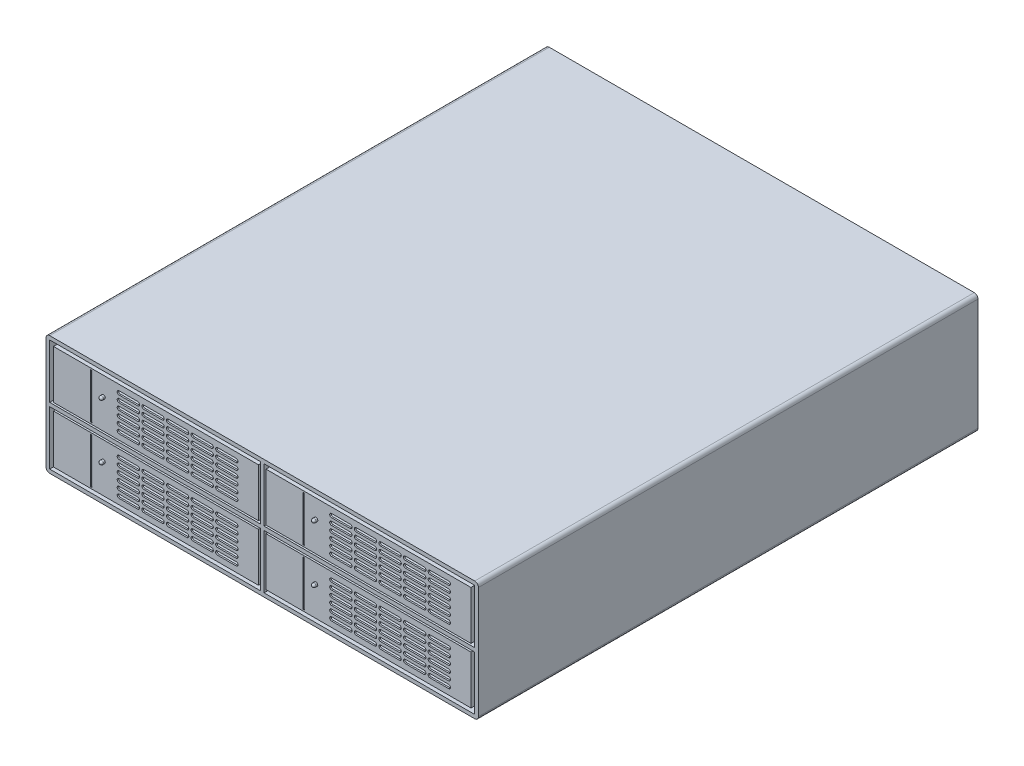
SolidWorks part; units mm, degrees
ref_plane "Front Plane" through (0, 0, 0) normal (0, 0, 1) x (1, 0, 0)
ref_plane "Top Plane" through (0, 0, 0) normal (0, 1, 0) x (1, 0, 0)
ref_plane "Right Plane" through (0, 0, 0) normal (1, 0, 0) x (0, 0, -1)
sketch "Sketch1" plane through (0, 0, 0) normal (0, 0, 1) x (1, 0, 0)
  line L1 (-73.66, 20.32) -> (73.66, 20.32)
  line L2 (-73.66, 20.32) -> (-73.66, -20.32)
  line L3 (-73.66, -20.32) -> (73.66, -20.32)
  line L4 (73.66, 20.32) -> (73.66, -20.32)
  line L5 (-73.66, 20.32) -> (73.66, -20.32) construction
  line L6 (-73.66, -20.32) -> (73.66, 20.32) construction
  point P0 (0, 0)
  dimension "D1" = 40.64
  dimension "D2" = 147.32
extrude "Boss-Extrude1" add sketch "Sketch1" against normal blind 170.18
sketch "Sketch2" plane through (0, 0, 0) normal (0, 0, 1) x (1, 0, 0)
  line L0 (73.66, 20.32) -> (-73.66, 20.32) construction
  line L1 (-71.12, 17.78) -> (-1.27, 17.78)
  line L2 (-71.12, 17.78) -> (-71.12, 1.27)
  line L3 (-71.12, 1.27) -> (-1.27, 1.27)
  line L4 (-1.27, 17.78) -> (-1.27, 1.27)
  line L5 (1.27, 17.78) -> (71.12, 17.78)
  line L6 (1.27, 17.78) -> (1.27, 1.27)
  line L7 (1.27, 1.27) -> (71.12, 1.27)
  line L8 (71.12, 17.78) -> (71.12, 1.27)
  line L9 (71.12, -1.27) -> (1.27, -1.27)
  line L10 (71.12, -1.27) -> (71.12, -17.78)
  line L11 (71.12, -17.78) -> (1.27, -17.78)
  line L12 (1.27, -1.27) -> (1.27, -17.78)
  line L13 (-1.27, -1.27) -> (-71.12, -1.27)
  line L14 (-1.27, -1.27) -> (-1.27, -17.78)
  line L15 (-1.27, -17.78) -> (-71.12, -17.78)
  line L16 (-71.12, -1.27) -> (-71.12, -17.78)
  line L17 (-73.66, 20.32) -> (-73.66, -20.32) construction
  line L18 (-73.66, -20.32) -> (73.66, -20.32) construction
  line L19 (73.66, -20.32) -> (73.66, 20.32) construction
  line L21 (-72.39, 19.05) -> (-0.635, 19.05)
  line L22 (-72.39, 19.05) -> (-72.39, 0.635)
  line L23 (-72.39, 0.635) -> (-0.635, 0.635)
  line L24 (-0.635, 19.05) -> (-0.635, 0.635)
  line L25 (-72.39, -0.635) -> (-0.635, -0.635)
  line L26 (-72.39, -0.635) -> (-72.39, -19.05)
  line L27 (-72.39, -19.05) -> (-0.635, -19.05)
  line L28 (-0.635, -0.635) -> (-0.635, -19.05)
  line L29 (0.635, -0.635) -> (72.39, -0.635)
  line L30 (0.635, -0.635) -> (0.635, -19.05)
  line L31 (0.635, -19.05) -> (72.39, -19.05)
  line L32 (72.39, -0.635) -> (72.39, -19.05)
  line L33 (72.39, 19.05) -> (0.635, 19.05)
  line L34 (72.39, 19.05) -> (72.39, 0.635)
  line L35 (72.39, 0.635) -> (0.635, 0.635)
  line L36 (0.635, 19.05) -> (0.635, 0.635)
  dimension "D1" = 2.54
  dimension "D2" = 2.54
  dimension "D3" = 2.54
  dimension "D4" = 2.54
  dimension "D5" = 2.54
  dimension "D6" = 2.54
  dimension "D7" = 2.54
  dimension "D8" = 2.54
  dimension "D9" = 2.54
  dimension "D10" = 16.51
  dimension "D11" = 2.54
  dimension "D12" = 16.51
  dimension "D13" = 2.54
  dimension "D14" = 2.54
  dimension "D15" = 69.85
  dimension "D16" = 69.85
  dimension "D17" = 1.27
  dimension "D18" = 1.27
  dimension "D19" = 1.27
  dimension "D20" = 1.27
  dimension "D21" = 0.635
  dimension "D22" = 0.635
  dimension "D23" = 1.27
  dimension "D24" = 1.27
  dimension "D25" = 0.635
  dimension "D26" = 0.635
  dimension "D27" = 1.27
  dimension "D28" = 0.635
  dimension "D29" = 1.27
  dimension "D30" = 0.635
  dimension "D31" = 0.635
  dimension "D32" = 1.27
extrude "Cut-Extrude1" cut sketch "Sketch2" against normal blind 152.4
fillet "Fillet1" radius 1.27 4 edges at (-73.66, 20.32, -85.09) (-73.66, -20.32, -85.09) (73.66, -20.32, -85.09) (73.66, 20.32, -85.09)
sketch "Sketch4" plane through (0, 0, 0) normal (0, 0, 1) x (1, 0, 0)
  line L0 (-73.66, 0) -> (73.66, 0) construction
  line L1 (-73.66, 19.05) -> (-73.66, -19.05) construction
  line L2 (73.66, -19.05) -> (73.66, 19.05) construction
  line L3 (-8.89, 3.81) -> (-15.24, 3.81) construction
  line L4 (-8.89, 3.175) -> (-15.24, 3.175)
  line L5 (-8.89, 4.445) -> (-15.24, 4.445)
  line L7 (-8.89, 6.096) -> (-15.24, 6.096) construction
  line L8 (-8.89, 5.461) -> (-15.24, 5.461)
  line L9 (-8.89, 6.731) -> (-15.24, 6.731)
  line L10 (-8.89, 8.382) -> (-15.24, 8.382) construction
  line L11 (-8.89, 7.747) -> (-15.24, 7.747)
  line L12 (-8.89, 9.017) -> (-15.24, 9.017)
  line L13 (-8.89, 10.668) -> (-15.24, 10.668) construction
  line L14 (-8.89, 10.033) -> (-15.24, 10.033)
  line L15 (-8.89, 11.303) -> (-15.24, 11.303)
  line L16 (-8.89, 12.954) -> (-15.24, 12.954) construction
  line L17 (-8.89, 12.319) -> (-15.24, 12.319)
  line L18 (-8.89, 13.589) -> (-15.24, 13.589)
  line L19 (-8.89, 15.24) -> (-15.24, 15.24) construction
  line L20 (-8.89, 14.605) -> (-15.24, 14.605)
  line L21 (-8.89, 15.875) -> (-15.24, 15.875)
  line L22 (-71.12, 1.27) -> (-1.27, 1.27) construction
  line L23 (-1.27, 1.27) -> (-1.27, 17.78) construction
  line L24 (-17.272, 3.81) -> (-23.622, 3.81) construction
  line L25 (-17.272, 3.175) -> (-23.622, 3.175)
  line L26 (-17.272, 4.445) -> (-23.622, 4.445)
  line L27 (-17.272, 6.096) -> (-23.622, 6.096) construction
  line L28 (-17.272, 5.461) -> (-23.622, 5.461)
  line L29 (-17.272, 6.731) -> (-23.622, 6.731)
  line L30 (-17.272, 8.382) -> (-23.622, 8.382) construction
  line L31 (-17.272, 7.747) -> (-23.622, 7.747)
  line L32 (-17.272, 9.017) -> (-23.622, 9.017)
  line L33 (-17.272, 10.668) -> (-23.622, 10.668) construction
  line L34 (-17.272, 10.033) -> (-23.622, 10.033)
  line L35 (-17.272, 11.303) -> (-23.622, 11.303)
  line L36 (-17.272, 12.954) -> (-23.622, 12.954) construction
  line L37 (-17.272, 12.319) -> (-23.622, 12.319)
  line L38 (-17.272, 13.589) -> (-23.622, 13.589)
  line L39 (-17.272, 15.24) -> (-23.622, 15.24) construction
  line L40 (-17.272, 14.605) -> (-23.622, 14.605)
  line L41 (-17.272, 15.875) -> (-23.622, 15.875)
  line L42 (-25.654, 3.81) -> (-32.004, 3.81) construction
  line L43 (-25.654, 3.175) -> (-32.004, 3.175)
  line L44 (-25.654, 4.445) -> (-32.004, 4.445)
  line L45 (-25.654, 6.096) -> (-32.004, 6.096) construction
  line L46 (-25.654, 5.461) -> (-32.004, 5.461)
  line L47 (-25.654, 6.731) -> (-32.004, 6.731)
  line L48 (-25.654, 8.382) -> (-32.004, 8.382) construction
  line L49 (-25.654, 7.747) -> (-32.004, 7.747)
  line L50 (-25.654, 9.017) -> (-32.004, 9.017)
  line L51 (-25.654, 10.668) -> (-32.004, 10.668) construction
  line L52 (-25.654, 10.033) -> (-32.004, 10.033)
  line L53 (-25.654, 11.303) -> (-32.004, 11.303)
  line L54 (-25.654, 12.954) -> (-32.004, 12.954) construction
  line L55 (-25.654, 12.319) -> (-32.004, 12.319)
  line L56 (-25.654, 13.589) -> (-32.004, 13.589)
  line L57 (-25.654, 15.24) -> (-32.004, 15.24) construction
  line L58 (-25.654, 14.605) -> (-32.004, 14.605)
  line L59 (-25.654, 15.875) -> (-32.004, 15.875)
  line L60 (-34.036, 3.81) -> (-40.386, 3.81) construction
  line L61 (-34.036, 3.175) -> (-40.386, 3.175)
  line L62 (-34.036, 4.445) -> (-40.386, 4.445)
  line L63 (-34.036, 6.096) -> (-40.386, 6.096) construction
  line L64 (-34.036, 5.461) -> (-40.386, 5.461)
  line L65 (-34.036, 6.731) -> (-40.386, 6.731)
  line L66 (-34.036, 8.382) -> (-40.386, 8.382) construction
  line L67 (-34.036, 7.747) -> (-40.386, 7.747)
  line L68 (-34.036, 9.017) -> (-40.386, 9.017)
  line L69 (-34.036, 10.668) -> (-40.386, 10.668) construction
  line L70 (-34.036, 10.033) -> (-40.386, 10.033)
  line L71 (-34.036, 11.303) -> (-40.386, 11.303)
  line L72 (-34.036, 12.954) -> (-40.386, 12.954) construction
  line L73 (-34.036, 12.319) -> (-40.386, 12.319)
  line L74 (-34.036, 13.589) -> (-40.386, 13.589)
  line L75 (-34.036, 15.24) -> (-40.386, 15.24) construction
  line L76 (-34.036, 14.605) -> (-40.386, 14.605)
  line L77 (-34.036, 15.875) -> (-40.386, 15.875)
  line L78 (-42.418, 3.81) -> (-48.768, 3.81) construction
  line L79 (-42.418, 3.175) -> (-48.768, 3.175)
  line L80 (-42.418, 4.445) -> (-48.768, 4.445)
  line L81 (-42.418, 6.096) -> (-48.768, 6.096) construction
  line L82 (-42.418, 5.461) -> (-48.768, 5.461)
  line L83 (-42.418, 6.731) -> (-48.768, 6.731)
  line L84 (-42.418, 8.382) -> (-48.768, 8.382) construction
  line L85 (-42.418, 7.747) -> (-48.768, 7.747)
  line L86 (-42.418, 9.017) -> (-48.768, 9.017)
  line L87 (-42.418, 10.668) -> (-48.768, 10.668) construction
  line L88 (-42.418, 10.033) -> (-48.768, 10.033)
  line L89 (-42.418, 11.303) -> (-48.768, 11.303)
  line L90 (-42.418, 12.954) -> (-48.768, 12.954) construction
  line L91 (-42.418, 12.319) -> (-48.768, 12.319)
  line L92 (-42.418, 13.589) -> (-48.768, 13.589)
  line L93 (-42.418, 15.24) -> (-48.768, 15.24) construction
  line L94 (-42.418, 14.605) -> (-48.768, 14.605)
  line L95 (-42.418, 15.875) -> (-48.768, 15.875)
  line L96 (-42.418, -15.24) -> (-48.768, -15.24) construction
  line L97 (-42.418, -14.605) -> (-48.768, -14.605)
  line L98 (-42.418, -15.875) -> (-48.768, -15.875)
  line L99 (-42.418, -12.954) -> (-48.768, -12.954) construction
  line L100 (-42.418, -12.319) -> (-48.768, -12.319)
  line L101 (-42.418, -13.589) -> (-48.768, -13.589)
  line L102 (-42.418, -10.668) -> (-48.768, -10.668) construction
  line L103 (-42.418, -10.033) -> (-48.768, -10.033)
  line L104 (-42.418, -11.303) -> (-48.768, -11.303)
  line L105 (-42.418, -8.382) -> (-48.768, -8.382) construction
  line L106 (-42.418, -7.747) -> (-48.768, -7.747)
  line L107 (-42.418, -9.017) -> (-48.768, -9.017)
  line L108 (-42.418, -6.096) -> (-48.768, -6.096) construction
  line L109 (-42.418, -5.461) -> (-48.768, -5.461)
  line L110 (-42.418, -6.731) -> (-48.768, -6.731)
  line L111 (-42.418, -3.81) -> (-48.768, -3.81) construction
  line L112 (-42.418, -3.175) -> (-48.768, -3.175)
  line L113 (-42.418, -4.445) -> (-48.768, -4.445)
  line L114 (-34.036, -15.24) -> (-40.386, -15.24) construction
  line L115 (-34.036, -14.605) -> (-40.386, -14.605)
  line L116 (-34.036, -15.875) -> (-40.386, -15.875)
  line L117 (-34.036, -12.954) -> (-40.386, -12.954) construction
  line L118 (-34.036, -12.319) -> (-40.386, -12.319)
  line L119 (-34.036, -13.589) -> (-40.386, -13.589)
  line L120 (-34.036, -10.668) -> (-40.386, -10.668) construction
  line L121 (-34.036, -10.033) -> (-40.386, -10.033)
  line L122 (-34.036, -11.303) -> (-40.386, -11.303)
  line L123 (-34.036, -8.382) -> (-40.386, -8.382) construction
  line L124 (-34.036, -7.747) -> (-40.386, -7.747)
  line L125 (-34.036, -9.017) -> (-40.386, -9.017)
  line L126 (-34.036, -6.096) -> (-40.386, -6.096) construction
  line L127 (-34.036, -5.461) -> (-40.386, -5.461)
  line L128 (-34.036, -6.731) -> (-40.386, -6.731)
  line L129 (-34.036, -3.81) -> (-40.386, -3.81) construction
  line L130 (-34.036, -3.175) -> (-40.386, -3.175)
  line L131 (-34.036, -4.445) -> (-40.386, -4.445)
  line L132 (-25.654, -15.24) -> (-32.004, -15.24) construction
  line L133 (-25.654, -14.605) -> (-32.004, -14.605)
  line L134 (-25.654, -15.875) -> (-32.004, -15.875)
  line L135 (-25.654, -12.954) -> (-32.004, -12.954) construction
  line L136 (-25.654, -12.319) -> (-32.004, -12.319)
  line L137 (-25.654, -13.589) -> (-32.004, -13.589)
  line L138 (-25.654, -10.668) -> (-32.004, -10.668) construction
  line L139 (-25.654, -10.033) -> (-32.004, -10.033)
  line L140 (-25.654, -11.303) -> (-32.004, -11.303)
  line L141 (-25.654, -8.382) -> (-32.004, -8.382) construction
  line L142 (-25.654, -7.747) -> (-32.004, -7.747)
  line L143 (-25.654, -9.017) -> (-32.004, -9.017)
  line L144 (-25.654, -6.096) -> (-32.004, -6.096) construction
  line L145 (-25.654, -5.461) -> (-32.004, -5.461)
  line L146 (-25.654, -6.731) -> (-32.004, -6.731)
  line L147 (-25.654, -3.81) -> (-32.004, -3.81) construction
  line L148 (-25.654, -3.175) -> (-32.004, -3.175)
  line L149 (-25.654, -4.445) -> (-32.004, -4.445)
  line L150 (-17.272, -15.24) -> (-23.622, -15.24) construction
  line L151 (-17.272, -14.605) -> (-23.622, -14.605)
  line L152 (-17.272, -15.875) -> (-23.622, -15.875)
  line L153 (-17.272, -12.954) -> (-23.622, -12.954) construction
  line L154 (-17.272, -12.319) -> (-23.622, -12.319)
  line L155 (-17.272, -13.589) -> (-23.622, -13.589)
  line L156 (-17.272, -10.668) -> (-23.622, -10.668) construction
  line L157 (-17.272, -10.033) -> (-23.622, -10.033)
  line L158 (-17.272, -11.303) -> (-23.622, -11.303)
  line L159 (-17.272, -8.382) -> (-23.622, -8.382) construction
  line L160 (-17.272, -7.747) -> (-23.622, -7.747)
  line L161 (-17.272, -9.017) -> (-23.622, -9.017)
  line L162 (-17.272, -6.096) -> (-23.622, -6.096) construction
  line L163 (-17.272, -5.461) -> (-23.622, -5.461)
  line L164 (-17.272, -6.731) -> (-23.622, -6.731)
  line L165 (-17.272, -3.81) -> (-23.622, -3.81) construction
  line L166 (-17.272, -3.175) -> (-23.622, -3.175)
  line L167 (-17.272, -4.445) -> (-23.622, -4.445)
  line L168 (-8.89, -15.24) -> (-15.24, -15.24) construction
  line L169 (-8.89, -14.605) -> (-15.24, -14.605)
  line L170 (-8.89, -15.875) -> (-15.24, -15.875)
  line L171 (-8.89, -12.954) -> (-15.24, -12.954) construction
  line L172 (-8.89, -12.319) -> (-15.24, -12.319)
  line L173 (-8.89, -13.589) -> (-15.24, -13.589)
  line L174 (-8.89, -10.668) -> (-15.24, -10.668) construction
  line L175 (-8.89, -10.033) -> (-15.24, -10.033)
  line L176 (-8.89, -11.303) -> (-15.24, -11.303)
  line L177 (-8.89, -8.382) -> (-15.24, -8.382) construction
  line L178 (-8.89, -7.747) -> (-15.24, -7.747)
  line L179 (-8.89, -9.017) -> (-15.24, -9.017)
  line L180 (-8.89, -6.096) -> (-15.24, -6.096) construction
  line L181 (-8.89, -5.461) -> (-15.24, -5.461)
  line L182 (-8.89, -6.731) -> (-15.24, -6.731)
  line L183 (-8.89, -3.81) -> (-15.24, -3.81) construction
  line L184 (-8.89, -3.175) -> (-15.24, -3.175)
  line L185 (-8.89, -4.445) -> (-15.24, -4.445)
  line L186 (63.5, 3.81) -> (57.15, 3.81) construction
  line L187 (63.5, 3.175) -> (57.15, 3.175)
  line L188 (63.5, 4.445) -> (57.15, 4.445)
  line L189 (63.5, 6.096) -> (57.15, 6.096) construction
  line L190 (63.5, 5.461) -> (57.15, 5.461)
  line L191 (63.5, 6.731) -> (57.15, 6.731)
  line L192 (63.5, 8.382) -> (57.15, 8.382) construction
  line L193 (63.5, 7.747) -> (57.15, 7.747)
  line L194 (63.5, 9.017) -> (57.15, 9.017)
  line L195 (63.5, 10.668) -> (57.15, 10.668) construction
  line L196 (63.5, 10.033) -> (57.15, 10.033)
  line L197 (63.5, 11.303) -> (57.15, 11.303)
  line L198 (63.5, 12.954) -> (57.15, 12.954) construction
  line L199 (63.5, 12.319) -> (57.15, 12.319)
  line L200 (63.5, 13.589) -> (57.15, 13.589)
  line L201 (63.5, 15.24) -> (57.15, 15.24) construction
  line L202 (63.5, 14.605) -> (57.15, 14.605)
  line L203 (63.5, 15.875) -> (57.15, 15.875)
  line L204 (55.118, 3.81) -> (48.768, 3.81) construction
  line L205 (55.118, 3.175) -> (48.768, 3.175)
  line L206 (55.118, 4.445) -> (48.768, 4.445)
  line L207 (55.118, 6.096) -> (48.768, 6.096) construction
  line L208 (55.118, 5.461) -> (48.768, 5.461)
  line L209 (55.118, 6.731) -> (48.768, 6.731)
  line L210 (55.118, 8.382) -> (48.768, 8.382) construction
  line L211 (55.118, 7.747) -> (48.768, 7.747)
  line L212 (55.118, 9.017) -> (48.768, 9.017)
  line L213 (55.118, 10.668) -> (48.768, 10.668) construction
  line L214 (55.118, 10.033) -> (48.768, 10.033)
  line L215 (55.118, 11.303) -> (48.768, 11.303)
  line L216 (55.118, 12.954) -> (48.768, 12.954) construction
  line L217 (55.118, 12.319) -> (48.768, 12.319)
  line L218 (55.118, 13.589) -> (48.768, 13.589)
  line L219 (55.118, 15.24) -> (48.768, 15.24) construction
  line L220 (55.118, 14.605) -> (48.768, 14.605)
  line L221 (55.118, 15.875) -> (48.768, 15.875)
  line L222 (46.736, 3.81) -> (40.386, 3.81) construction
  line L223 (46.736, 3.175) -> (40.386, 3.175)
  line L224 (46.736, 4.445) -> (40.386, 4.445)
  line L225 (46.736, 6.096) -> (40.386, 6.096) construction
  line L226 (46.736, 5.461) -> (40.386, 5.461)
  line L227 (46.736, 6.731) -> (40.386, 6.731)
  line L228 (46.736, 8.382) -> (40.386, 8.382) construction
  line L229 (46.736, 7.747) -> (40.386, 7.747)
  line L230 (46.736, 9.017) -> (40.386, 9.017)
  line L231 (46.736, 10.668) -> (40.386, 10.668) construction
  line L232 (46.736, 10.033) -> (40.386, 10.033)
  line L233 (46.736, 11.303) -> (40.386, 11.303)
  line L234 (46.736, 12.954) -> (40.386, 12.954) construction
  line L235 (46.736, 12.319) -> (40.386, 12.319)
  line L236 (46.736, 13.589) -> (40.386, 13.589)
  line L237 (46.736, 15.24) -> (40.386, 15.24) construction
  line L238 (46.736, 14.605) -> (40.386, 14.605)
  line L239 (46.736, 15.875) -> (40.386, 15.875)
  line L240 (38.354, 3.81) -> (32.004, 3.81) construction
  line L241 (38.354, 3.175) -> (32.004, 3.175)
  line L242 (38.354, 4.445) -> (32.004, 4.445)
  line L243 (38.354, 6.096) -> (32.004, 6.096) construction
  line L244 (38.354, 5.461) -> (32.004, 5.461)
  line L245 (38.354, 6.731) -> (32.004, 6.731)
  line L246 (38.354, 8.382) -> (32.004, 8.382) construction
  line L247 (38.354, 7.747) -> (32.004, 7.747)
  line L248 (38.354, 9.017) -> (32.004, 9.017)
  line L249 (38.354, 10.668) -> (32.004, 10.668) construction
  line L250 (38.354, 10.033) -> (32.004, 10.033)
  line L251 (38.354, 11.303) -> (32.004, 11.303)
  line L252 (38.354, 12.954) -> (32.004, 12.954) construction
  line L253 (38.354, 12.319) -> (32.004, 12.319)
  line L254 (38.354, 13.589) -> (32.004, 13.589)
  line L255 (38.354, 15.24) -> (32.004, 15.24) construction
  line L256 (38.354, 14.605) -> (32.004, 14.605)
  line L257 (38.354, 15.875) -> (32.004, 15.875)
  line L258 (29.972, 3.81) -> (23.622, 3.81) construction
  line L259 (29.972, 3.175) -> (23.622, 3.175)
  line L260 (29.972, 4.445) -> (23.622, 4.445)
  line L261 (29.972, 6.096) -> (23.622, 6.096) construction
  line L262 (29.972, 5.461) -> (23.622, 5.461)
  line L263 (29.972, 6.731) -> (23.622, 6.731)
  line L264 (29.972, 8.382) -> (23.622, 8.382) construction
  line L265 (29.972, 7.747) -> (23.622, 7.747)
  line L266 (29.972, 9.017) -> (23.622, 9.017)
  line L267 (29.972, 10.668) -> (23.622, 10.668) construction
  line L268 (29.972, 10.033) -> (23.622, 10.033)
  line L269 (29.972, 11.303) -> (23.622, 11.303)
  line L270 (29.972, 12.954) -> (23.622, 12.954) construction
  line L271 (29.972, 12.319) -> (23.622, 12.319)
  line L272 (29.972, 13.589) -> (23.622, 13.589)
  line L273 (29.972, 15.24) -> (23.622, 15.24) construction
  line L274 (29.972, 14.605) -> (23.622, 14.605)
  line L275 (29.972, 15.875) -> (23.622, 15.875)
  line L276 (71.12, 1.27) -> (71.12, 17.78) construction
  line L277 (1.27, 1.27) -> (71.12, 1.27) construction
  line L278 (29.972, -15.24) -> (23.622, -15.24) construction
  line L279 (29.972, -14.605) -> (23.622, -14.605)
  line L280 (29.972, -15.875) -> (23.622, -15.875)
  line L281 (29.972, -12.954) -> (23.622, -12.954) construction
  line L282 (29.972, -12.319) -> (23.622, -12.319)
  line L283 (29.972, -13.589) -> (23.622, -13.589)
  line L284 (29.972, -10.668) -> (23.622, -10.668) construction
  line L285 (29.972, -10.033) -> (23.622, -10.033)
  line L286 (29.972, -11.303) -> (23.622, -11.303)
  line L287 (29.972, -8.382) -> (23.622, -8.382) construction
  line L288 (29.972, -7.747) -> (23.622, -7.747)
  line L289 (29.972, -9.017) -> (23.622, -9.017)
  line L290 (29.972, -6.096) -> (23.622, -6.096) construction
  line L291 (29.972, -5.461) -> (23.622, -5.461)
  line L292 (29.972, -6.731) -> (23.622, -6.731)
  line L293 (29.972, -3.81) -> (23.622, -3.81) construction
  line L294 (29.972, -3.175) -> (23.622, -3.175)
  line L295 (29.972, -4.445) -> (23.622, -4.445)
  line L296 (38.354, -15.24) -> (32.004, -15.24) construction
  line L297 (38.354, -14.605) -> (32.004, -14.605)
  line L298 (38.354, -15.875) -> (32.004, -15.875)
  line L299 (38.354, -12.954) -> (32.004, -12.954) construction
  line L300 (38.354, -12.319) -> (32.004, -12.319)
  line L301 (38.354, -13.589) -> (32.004, -13.589)
  line L302 (38.354, -10.668) -> (32.004, -10.668) construction
  line L303 (38.354, -10.033) -> (32.004, -10.033)
  line L304 (38.354, -11.303) -> (32.004, -11.303)
  line L305 (38.354, -8.382) -> (32.004, -8.382) construction
  line L306 (38.354, -7.747) -> (32.004, -7.747)
  line L307 (38.354, -9.017) -> (32.004, -9.017)
  line L308 (38.354, -6.096) -> (32.004, -6.096) construction
  line L309 (38.354, -5.461) -> (32.004, -5.461)
  line L310 (38.354, -6.731) -> (32.004, -6.731)
  line L311 (38.354, -3.81) -> (32.004, -3.81) construction
  line L312 (38.354, -3.175) -> (32.004, -3.175)
  line L313 (38.354, -4.445) -> (32.004, -4.445)
  line L314 (46.736, -15.24) -> (40.386, -15.24) construction
  line L315 (46.736, -14.605) -> (40.386, -14.605)
  line L316 (46.736, -15.875) -> (40.386, -15.875)
  line L317 (46.736, -12.954) -> (40.386, -12.954) construction
  line L318 (46.736, -12.319) -> (40.386, -12.319)
  line L319 (46.736, -13.589) -> (40.386, -13.589)
  line L320 (46.736, -10.668) -> (40.386, -10.668) construction
  line L321 (46.736, -10.033) -> (40.386, -10.033)
  line L322 (46.736, -11.303) -> (40.386, -11.303)
  line L323 (46.736, -8.382) -> (40.386, -8.382) construction
  line L324 (46.736, -7.747) -> (40.386, -7.747)
  line L325 (46.736, -9.017) -> (40.386, -9.017)
  line L326 (46.736, -6.096) -> (40.386, -6.096) construction
  line L327 (46.736, -5.461) -> (40.386, -5.461)
  line L328 (46.736, -6.731) -> (40.386, -6.731)
  line L329 (46.736, -3.81) -> (40.386, -3.81) construction
  line L330 (46.736, -3.175) -> (40.386, -3.175)
  line L331 (46.736, -4.445) -> (40.386, -4.445)
  line L332 (55.118, -15.24) -> (48.768, -15.24) construction
  line L333 (55.118, -14.605) -> (48.768, -14.605)
  line L334 (55.118, -15.875) -> (48.768, -15.875)
  line L335 (55.118, -12.954) -> (48.768, -12.954) construction
  line L336 (55.118, -12.319) -> (48.768, -12.319)
  line L337 (55.118, -13.589) -> (48.768, -13.589)
  line L338 (55.118, -10.668) -> (48.768, -10.668) construction
  line L339 (55.118, -10.033) -> (48.768, -10.033)
  line L340 (55.118, -11.303) -> (48.768, -11.303)
  line L341 (55.118, -8.382) -> (48.768, -8.382) construction
  line L342 (55.118, -7.747) -> (48.768, -7.747)
  line L343 (55.118, -9.017) -> (48.768, -9.017)
  line L344 (55.118, -6.096) -> (48.768, -6.096) construction
  line L345 (55.118, -5.461) -> (48.768, -5.461)
  line L346 (55.118, -6.731) -> (48.768, -6.731)
  line L347 (55.118, -3.81) -> (48.768, -3.81) construction
  line L348 (55.118, -3.175) -> (48.768, -3.175)
  line L349 (55.118, -4.445) -> (48.768, -4.445)
  line L350 (63.5, -15.24) -> (57.15, -15.24) construction
  line L351 (63.5, -14.605) -> (57.15, -14.605)
  line L352 (63.5, -15.875) -> (57.15, -15.875)
  line L353 (63.5, -12.954) -> (57.15, -12.954) construction
  line L354 (63.5, -12.319) -> (57.15, -12.319)
  line L355 (63.5, -13.589) -> (57.15, -13.589)
  line L356 (63.5, -10.668) -> (57.15, -10.668) construction
  line L357 (63.5, -10.033) -> (57.15, -10.033)
  line L358 (63.5, -11.303) -> (57.15, -11.303)
  line L359 (63.5, -8.382) -> (57.15, -8.382) construction
  line L360 (63.5, -7.747) -> (57.15, -7.747)
  line L361 (63.5, -9.017) -> (57.15, -9.017)
  line L362 (63.5, -6.096) -> (57.15, -6.096) construction
  line L363 (63.5, -5.461) -> (57.15, -5.461)
  line L364 (63.5, -6.731) -> (57.15, -6.731)
  line L365 (63.5, -3.81) -> (57.15, -3.81) construction
  line L366 (63.5, -3.175) -> (57.15, -3.175)
  line L367 (63.5, -4.445) -> (57.15, -4.445)
  arc A0 (-8.89, 3.175) -> (-8.89, 4.445) centre (-8.89, 3.81) ccw
  arc A1 (-15.24, 4.445) -> (-15.24, 3.175) centre (-15.24, 3.81) ccw
  arc A2 (-8.89, 5.461) -> (-8.89, 6.731) centre (-8.89, 6.096) ccw
  arc A3 (-15.24, 6.731) -> (-15.24, 5.461) centre (-15.24, 6.096) ccw
  arc A4 (-8.89, 7.747) -> (-8.89, 9.017) centre (-8.89, 8.382) ccw
  arc A5 (-15.24, 9.017) -> (-15.24, 7.747) centre (-15.24, 8.382) ccw
  arc A6 (-8.89, 10.033) -> (-8.89, 11.303) centre (-8.89, 10.668) ccw
  arc A7 (-15.24, 11.303) -> (-15.24, 10.033) centre (-15.24, 10.668) ccw
  arc A8 (-8.89, 12.319) -> (-8.89, 13.589) centre (-8.89, 12.954) ccw
  arc A9 (-15.24, 13.589) -> (-15.24, 12.319) centre (-15.24, 12.954) ccw
  arc A10 (-8.89, 14.605) -> (-8.89, 15.875) centre (-8.89, 15.24) ccw
  arc A11 (-15.24, 15.875) -> (-15.24, 14.605) centre (-15.24, 15.24) ccw
  arc A12 (-17.272, 3.175) -> (-17.272, 4.445) centre (-17.272, 3.81) ccw
  arc A13 (-23.622, 4.445) -> (-23.622, 3.175) centre (-23.622, 3.81) ccw
  arc A14 (-17.272, 5.461) -> (-17.272, 6.731) centre (-17.272, 6.096) ccw
  arc A15 (-23.622, 6.731) -> (-23.622, 5.461) centre (-23.622, 6.096) ccw
  arc A16 (-17.272, 7.747) -> (-17.272, 9.017) centre (-17.272, 8.382) ccw
  arc A17 (-23.622, 9.017) -> (-23.622, 7.747) centre (-23.622, 8.382) ccw
  arc A18 (-17.272, 10.033) -> (-17.272, 11.303) centre (-17.272, 10.668) ccw
  arc A19 (-23.622, 11.303) -> (-23.622, 10.033) centre (-23.622, 10.668) ccw
  arc A20 (-17.272, 12.319) -> (-17.272, 13.589) centre (-17.272, 12.954) ccw
  arc A21 (-23.622, 13.589) -> (-23.622, 12.319) centre (-23.622, 12.954) ccw
  arc A22 (-17.272, 14.605) -> (-17.272, 15.875) centre (-17.272, 15.24) ccw
  arc A23 (-23.622, 15.875) -> (-23.622, 14.605) centre (-23.622, 15.24) ccw
  arc A24 (-25.654, 3.175) -> (-25.654, 4.445) centre (-25.654, 3.81) ccw
  arc A25 (-32.004, 4.445) -> (-32.004, 3.175) centre (-32.004, 3.81) ccw
  arc A26 (-25.654, 5.461) -> (-25.654, 6.731) centre (-25.654, 6.096) ccw
  arc A27 (-32.004, 6.731) -> (-32.004, 5.461) centre (-32.004, 6.096) ccw
  arc A28 (-25.654, 7.747) -> (-25.654, 9.017) centre (-25.654, 8.382) ccw
  arc A29 (-32.004, 9.017) -> (-32.004, 7.747) centre (-32.004, 8.382) ccw
  arc A30 (-25.654, 10.033) -> (-25.654, 11.303) centre (-25.654, 10.668) ccw
  arc A31 (-32.004, 11.303) -> (-32.004, 10.033) centre (-32.004, 10.668) ccw
  arc A32 (-25.654, 12.319) -> (-25.654, 13.589) centre (-25.654, 12.954) ccw
  arc A33 (-32.004, 13.589) -> (-32.004, 12.319) centre (-32.004, 12.954) ccw
  arc A34 (-25.654, 14.605) -> (-25.654, 15.875) centre (-25.654, 15.24) ccw
  arc A35 (-32.004, 15.875) -> (-32.004, 14.605) centre (-32.004, 15.24) ccw
  arc A36 (-34.036, 3.175) -> (-34.036, 4.445) centre (-34.036, 3.81) ccw
  arc A37 (-40.386, 4.445) -> (-40.386, 3.175) centre (-40.386, 3.81) ccw
  arc A38 (-34.036, 5.461) -> (-34.036, 6.731) centre (-34.036, 6.096) ccw
  arc A39 (-40.386, 6.731) -> (-40.386, 5.461) centre (-40.386, 6.096) ccw
  arc A40 (-34.036, 7.747) -> (-34.036, 9.017) centre (-34.036, 8.382) ccw
  arc A41 (-40.386, 9.017) -> (-40.386, 7.747) centre (-40.386, 8.382) ccw
  arc A42 (-34.036, 10.033) -> (-34.036, 11.303) centre (-34.036, 10.668) ccw
  arc A43 (-40.386, 11.303) -> (-40.386, 10.033) centre (-40.386, 10.668) ccw
  arc A44 (-34.036, 12.319) -> (-34.036, 13.589) centre (-34.036, 12.954) ccw
  arc A45 (-40.386, 13.589) -> (-40.386, 12.319) centre (-40.386, 12.954) ccw
  arc A46 (-34.036, 14.605) -> (-34.036, 15.875) centre (-34.036, 15.24) ccw
  arc A47 (-40.386, 15.875) -> (-40.386, 14.605) centre (-40.386, 15.24) ccw
  arc A48 (-42.418, 3.175) -> (-42.418, 4.445) centre (-42.418, 3.81) ccw
  arc A49 (-48.768, 4.445) -> (-48.768, 3.175) centre (-48.768, 3.81) ccw
  arc A50 (-42.418, 5.461) -> (-42.418, 6.731) centre (-42.418, 6.096) ccw
  arc A51 (-48.768, 6.731) -> (-48.768, 5.461) centre (-48.768, 6.096) ccw
  arc A52 (-42.418, 7.747) -> (-42.418, 9.017) centre (-42.418, 8.382) ccw
  arc A53 (-48.768, 9.017) -> (-48.768, 7.747) centre (-48.768, 8.382) ccw
  arc A54 (-42.418, 10.033) -> (-42.418, 11.303) centre (-42.418, 10.668) ccw
  arc A55 (-48.768, 11.303) -> (-48.768, 10.033) centre (-48.768, 10.668) ccw
  arc A56 (-42.418, 12.319) -> (-42.418, 13.589) centre (-42.418, 12.954) ccw
  arc A57 (-48.768, 13.589) -> (-48.768, 12.319) centre (-48.768, 12.954) ccw
  arc A58 (-42.418, 14.605) -> (-42.418, 15.875) centre (-42.418, 15.24) ccw
  arc A59 (-48.768, 15.875) -> (-48.768, 14.605) centre (-48.768, 15.24) ccw
  arc A60 (-42.418, -14.605) -> (-42.418, -15.875) centre (-42.418, -15.24) cw
  arc A61 (-48.768, -15.875) -> (-48.768, -14.605) centre (-48.768, -15.24) cw
  arc A62 (-42.418, -12.319) -> (-42.418, -13.589) centre (-42.418, -12.954) cw
  arc A63 (-48.768, -13.589) -> (-48.768, -12.319) centre (-48.768, -12.954) cw
  arc A64 (-42.418, -10.033) -> (-42.418, -11.303) centre (-42.418, -10.668) cw
  arc A65 (-48.768, -11.303) -> (-48.768, -10.033) centre (-48.768, -10.668) cw
  arc A66 (-42.418, -7.747) -> (-42.418, -9.017) centre (-42.418, -8.382) cw
  arc A67 (-48.768, -9.017) -> (-48.768, -7.747) centre (-48.768, -8.382) cw
  arc A68 (-42.418, -5.461) -> (-42.418, -6.731) centre (-42.418, -6.096) cw
  arc A69 (-48.768, -6.731) -> (-48.768, -5.461) centre (-48.768, -6.096) cw
  arc A70 (-42.418, -3.175) -> (-42.418, -4.445) centre (-42.418, -3.81) cw
  arc A71 (-48.768, -4.445) -> (-48.768, -3.175) centre (-48.768, -3.81) cw
  arc A72 (-34.036, -14.605) -> (-34.036, -15.875) centre (-34.036, -15.24) cw
  arc A73 (-40.386, -15.875) -> (-40.386, -14.605) centre (-40.386, -15.24) cw
  arc A74 (-34.036, -12.319) -> (-34.036, -13.589) centre (-34.036, -12.954) cw
  arc A75 (-40.386, -13.589) -> (-40.386, -12.319) centre (-40.386, -12.954) cw
  arc A76 (-34.036, -10.033) -> (-34.036, -11.303) centre (-34.036, -10.668) cw
  arc A77 (-40.386, -11.303) -> (-40.386, -10.033) centre (-40.386, -10.668) cw
  arc A78 (-34.036, -7.747) -> (-34.036, -9.017) centre (-34.036, -8.382) cw
  arc A79 (-40.386, -9.017) -> (-40.386, -7.747) centre (-40.386, -8.382) cw
  arc A80 (-34.036, -5.461) -> (-34.036, -6.731) centre (-34.036, -6.096) cw
  arc A81 (-40.386, -6.731) -> (-40.386, -5.461) centre (-40.386, -6.096) cw
  arc A82 (-34.036, -3.175) -> (-34.036, -4.445) centre (-34.036, -3.81) cw
  arc A83 (-40.386, -4.445) -> (-40.386, -3.175) centre (-40.386, -3.81) cw
  arc A84 (-25.654, -14.605) -> (-25.654, -15.875) centre (-25.654, -15.24) cw
  arc A85 (-32.004, -15.875) -> (-32.004, -14.605) centre (-32.004, -15.24) cw
  arc A86 (-25.654, -12.319) -> (-25.654, -13.589) centre (-25.654, -12.954) cw
  arc A87 (-32.004, -13.589) -> (-32.004, -12.319) centre (-32.004, -12.954) cw
  arc A88 (-25.654, -10.033) -> (-25.654, -11.303) centre (-25.654, -10.668) cw
  arc A89 (-32.004, -11.303) -> (-32.004, -10.033) centre (-32.004, -10.668) cw
  arc A90 (-25.654, -7.747) -> (-25.654, -9.017) centre (-25.654, -8.382) cw
  arc A91 (-32.004, -9.017) -> (-32.004, -7.747) centre (-32.004, -8.382) cw
  arc A92 (-25.654, -5.461) -> (-25.654, -6.731) centre (-25.654, -6.096) cw
  arc A93 (-32.004, -6.731) -> (-32.004, -5.461) centre (-32.004, -6.096) cw
  arc A94 (-25.654, -3.175) -> (-25.654, -4.445) centre (-25.654, -3.81) cw
  arc A95 (-32.004, -4.445) -> (-32.004, -3.175) centre (-32.004, -3.81) cw
  arc A96 (-17.272, -14.605) -> (-17.272, -15.875) centre (-17.272, -15.24) cw
  arc A97 (-23.622, -15.875) -> (-23.622, -14.605) centre (-23.622, -15.24) cw
  arc A98 (-17.272, -12.319) -> (-17.272, -13.589) centre (-17.272, -12.954) cw
  arc A99 (-23.622, -13.589) -> (-23.622, -12.319) centre (-23.622, -12.954) cw
  arc A100 (-17.272, -10.033) -> (-17.272, -11.303) centre (-17.272, -10.668) cw
  arc A101 (-23.622, -11.303) -> (-23.622, -10.033) centre (-23.622, -10.668) cw
  arc A102 (-17.272, -7.747) -> (-17.272, -9.017) centre (-17.272, -8.382) cw
  arc A103 (-23.622, -9.017) -> (-23.622, -7.747) centre (-23.622, -8.382) cw
  arc A104 (-17.272, -5.461) -> (-17.272, -6.731) centre (-17.272, -6.096) cw
  arc A105 (-23.622, -6.731) -> (-23.622, -5.461) centre (-23.622, -6.096) cw
  arc A106 (-17.272, -3.175) -> (-17.272, -4.445) centre (-17.272, -3.81) cw
  arc A107 (-23.622, -4.445) -> (-23.622, -3.175) centre (-23.622, -3.81) cw
  arc A108 (-8.89, -14.605) -> (-8.89, -15.875) centre (-8.89, -15.24) cw
  arc A109 (-15.24, -15.875) -> (-15.24, -14.605) centre (-15.24, -15.24) cw
  arc A110 (-8.89, -12.319) -> (-8.89, -13.589) centre (-8.89, -12.954) cw
  arc A111 (-15.24, -13.589) -> (-15.24, -12.319) centre (-15.24, -12.954) cw
  arc A112 (-8.89, -10.033) -> (-8.89, -11.303) centre (-8.89, -10.668) cw
  arc A113 (-15.24, -11.303) -> (-15.24, -10.033) centre (-15.24, -10.668) cw
  arc A114 (-8.89, -7.747) -> (-8.89, -9.017) centre (-8.89, -8.382) cw
  arc A115 (-15.24, -9.017) -> (-15.24, -7.747) centre (-15.24, -8.382) cw
  arc A116 (-8.89, -5.461) -> (-8.89, -6.731) centre (-8.89, -6.096) cw
  arc A117 (-15.24, -6.731) -> (-15.24, -5.461) centre (-15.24, -6.096) cw
  arc A118 (-8.89, -3.175) -> (-8.89, -4.445) centre (-8.89, -3.81) cw
  arc A119 (-15.24, -4.445) -> (-15.24, -3.175) centre (-15.24, -3.81) cw
  arc A120 (63.5, 3.175) -> (63.5, 4.445) centre (63.5, 3.81) ccw
  arc A121 (57.15, 4.445) -> (57.15, 3.175) centre (57.15, 3.81) ccw
  arc A122 (63.5, 5.461) -> (63.5, 6.731) centre (63.5, 6.096) ccw
  arc A123 (57.15, 6.731) -> (57.15, 5.461) centre (57.15, 6.096) ccw
  arc A124 (63.5, 7.747) -> (63.5, 9.017) centre (63.5, 8.382) ccw
  arc A125 (57.15, 9.017) -> (57.15, 7.747) centre (57.15, 8.382) ccw
  arc A126 (63.5, 10.033) -> (63.5, 11.303) centre (63.5, 10.668) ccw
  arc A127 (57.15, 11.303) -> (57.15, 10.033) centre (57.15, 10.668) ccw
  arc A128 (63.5, 12.319) -> (63.5, 13.589) centre (63.5, 12.954) ccw
  arc A129 (57.15, 13.589) -> (57.15, 12.319) centre (57.15, 12.954) ccw
  arc A130 (63.5, 14.605) -> (63.5, 15.875) centre (63.5, 15.24) ccw
  arc A131 (57.15, 15.875) -> (57.15, 14.605) centre (57.15, 15.24) ccw
  arc A132 (55.118, 3.175) -> (55.118, 4.445) centre (55.118, 3.81) ccw
  arc A133 (48.768, 4.445) -> (48.768, 3.175) centre (48.768, 3.81) ccw
  arc A134 (55.118, 5.461) -> (55.118, 6.731) centre (55.118, 6.096) ccw
  arc A135 (48.768, 6.731) -> (48.768, 5.461) centre (48.768, 6.096) ccw
  arc A136 (55.118, 7.747) -> (55.118, 9.017) centre (55.118, 8.382) ccw
  arc A137 (48.768, 9.017) -> (48.768, 7.747) centre (48.768, 8.382) ccw
  arc A138 (55.118, 10.033) -> (55.118, 11.303) centre (55.118, 10.668) ccw
  arc A139 (48.768, 11.303) -> (48.768, 10.033) centre (48.768, 10.668) ccw
  arc A140 (55.118, 12.319) -> (55.118, 13.589) centre (55.118, 12.954) ccw
  arc A141 (48.768, 13.589) -> (48.768, 12.319) centre (48.768, 12.954) ccw
  arc A142 (55.118, 14.605) -> (55.118, 15.875) centre (55.118, 15.24) ccw
  arc A143 (48.768, 15.875) -> (48.768, 14.605) centre (48.768, 15.24) ccw
  arc A144 (46.736, 3.175) -> (46.736, 4.445) centre (46.736, 3.81) ccw
  arc A145 (40.386, 4.445) -> (40.386, 3.175) centre (40.386, 3.81) ccw
  arc A146 (46.736, 5.461) -> (46.736, 6.731) centre (46.736, 6.096) ccw
  arc A147 (40.386, 6.731) -> (40.386, 5.461) centre (40.386, 6.096) ccw
  arc A148 (46.736, 7.747) -> (46.736, 9.017) centre (46.736, 8.382) ccw
  arc A149 (40.386, 9.017) -> (40.386, 7.747) centre (40.386, 8.382) ccw
  arc A150 (46.736, 10.033) -> (46.736, 11.303) centre (46.736, 10.668) ccw
  arc A151 (40.386, 11.303) -> (40.386, 10.033) centre (40.386, 10.668) ccw
  arc A152 (46.736, 12.319) -> (46.736, 13.589) centre (46.736, 12.954) ccw
  arc A153 (40.386, 13.589) -> (40.386, 12.319) centre (40.386, 12.954) ccw
  arc A154 (46.736, 14.605) -> (46.736, 15.875) centre (46.736, 15.24) ccw
  arc A155 (40.386, 15.875) -> (40.386, 14.605) centre (40.386, 15.24) ccw
  arc A156 (38.354, 3.175) -> (38.354, 4.445) centre (38.354, 3.81) ccw
  arc A157 (32.004, 4.445) -> (32.004, 3.175) centre (32.004, 3.81) ccw
  arc A158 (38.354, 5.461) -> (38.354, 6.731) centre (38.354, 6.096) ccw
  arc A159 (32.004, 6.731) -> (32.004, 5.461) centre (32.004, 6.096) ccw
  arc A160 (38.354, 7.747) -> (38.354, 9.017) centre (38.354, 8.382) ccw
  arc A161 (32.004, 9.017) -> (32.004, 7.747) centre (32.004, 8.382) ccw
  arc A162 (38.354, 10.033) -> (38.354, 11.303) centre (38.354, 10.668) ccw
  arc A163 (32.004, 11.303) -> (32.004, 10.033) centre (32.004, 10.668) ccw
  arc A164 (38.354, 12.319) -> (38.354, 13.589) centre (38.354, 12.954) ccw
  arc A165 (32.004, 13.589) -> (32.004, 12.319) centre (32.004, 12.954) ccw
  arc A166 (38.354, 14.605) -> (38.354, 15.875) centre (38.354, 15.24) ccw
  arc A167 (32.004, 15.875) -> (32.004, 14.605) centre (32.004, 15.24) ccw
  arc A168 (29.972, 3.175) -> (29.972, 4.445) centre (29.972, 3.81) ccw
  arc A169 (23.622, 4.445) -> (23.622, 3.175) centre (23.622, 3.81) ccw
  arc A170 (29.972, 5.461) -> (29.972, 6.731) centre (29.972, 6.096) ccw
  arc A171 (23.622, 6.731) -> (23.622, 5.461) centre (23.622, 6.096) ccw
  arc A172 (29.972, 7.747) -> (29.972, 9.017) centre (29.972, 8.382) ccw
  arc A173 (23.622, 9.017) -> (23.622, 7.747) centre (23.622, 8.382) ccw
  arc A174 (29.972, 10.033) -> (29.972, 11.303) centre (29.972, 10.668) ccw
  arc A175 (23.622, 11.303) -> (23.622, 10.033) centre (23.622, 10.668) ccw
  arc A176 (29.972, 12.319) -> (29.972, 13.589) centre (29.972, 12.954) ccw
  arc A177 (23.622, 13.589) -> (23.622, 12.319) centre (23.622, 12.954) ccw
  arc A178 (29.972, 14.605) -> (29.972, 15.875) centre (29.972, 15.24) ccw
  arc A179 (23.622, 15.875) -> (23.622, 14.605) centre (23.622, 15.24) ccw
  arc A180 (29.972, -14.605) -> (29.972, -15.875) centre (29.972, -15.24) cw
  arc A181 (23.622, -15.875) -> (23.622, -14.605) centre (23.622, -15.24) cw
  arc A182 (29.972, -12.319) -> (29.972, -13.589) centre (29.972, -12.954) cw
  arc A183 (23.622, -13.589) -> (23.622, -12.319) centre (23.622, -12.954) cw
  arc A184 (29.972, -10.033) -> (29.972, -11.303) centre (29.972, -10.668) cw
  arc A185 (23.622, -11.303) -> (23.622, -10.033) centre (23.622, -10.668) cw
  arc A186 (29.972, -7.747) -> (29.972, -9.017) centre (29.972, -8.382) cw
  arc A187 (23.622, -9.017) -> (23.622, -7.747) centre (23.622, -8.382) cw
  arc A188 (29.972, -5.461) -> (29.972, -6.731) centre (29.972, -6.096) cw
  arc A189 (23.622, -6.731) -> (23.622, -5.461) centre (23.622, -6.096) cw
  arc A190 (29.972, -3.175) -> (29.972, -4.445) centre (29.972, -3.81) cw
  arc A191 (23.622, -4.445) -> (23.622, -3.175) centre (23.622, -3.81) cw
  arc A192 (38.354, -14.605) -> (38.354, -15.875) centre (38.354, -15.24) cw
  arc A193 (32.004, -15.875) -> (32.004, -14.605) centre (32.004, -15.24) cw
  arc A194 (38.354, -12.319) -> (38.354, -13.589) centre (38.354, -12.954) cw
  arc A195 (32.004, -13.589) -> (32.004, -12.319) centre (32.004, -12.954) cw
  arc A196 (38.354, -10.033) -> (38.354, -11.303) centre (38.354, -10.668) cw
  arc A197 (32.004, -11.303) -> (32.004, -10.033) centre (32.004, -10.668) cw
  arc A198 (38.354, -7.747) -> (38.354, -9.017) centre (38.354, -8.382) cw
  arc A199 (32.004, -9.017) -> (32.004, -7.747) centre (32.004, -8.382) cw
  arc A200 (38.354, -5.461) -> (38.354, -6.731) centre (38.354, -6.096) cw
  arc A201 (32.004, -6.731) -> (32.004, -5.461) centre (32.004, -6.096) cw
  arc A202 (38.354, -3.175) -> (38.354, -4.445) centre (38.354, -3.81) cw
  arc A203 (32.004, -4.445) -> (32.004, -3.175) centre (32.004, -3.81) cw
  arc A204 (46.736, -14.605) -> (46.736, -15.875) centre (46.736, -15.24) cw
  arc A205 (40.386, -15.875) -> (40.386, -14.605) centre (40.386, -15.24) cw
  arc A206 (46.736, -12.319) -> (46.736, -13.589) centre (46.736, -12.954) cw
  arc A207 (40.386, -13.589) -> (40.386, -12.319) centre (40.386, -12.954) cw
  arc A208 (46.736, -10.033) -> (46.736, -11.303) centre (46.736, -10.668) cw
  arc A209 (40.386, -11.303) -> (40.386, -10.033) centre (40.386, -10.668) cw
  arc A210 (46.736, -7.747) -> (46.736, -9.017) centre (46.736, -8.382) cw
  arc A211 (40.386, -9.017) -> (40.386, -7.747) centre (40.386, -8.382) cw
  arc A212 (46.736, -5.461) -> (46.736, -6.731) centre (46.736, -6.096) cw
  arc A213 (40.386, -6.731) -> (40.386, -5.461) centre (40.386, -6.096) cw
  arc A214 (46.736, -3.175) -> (46.736, -4.445) centre (46.736, -3.81) cw
  arc A215 (40.386, -4.445) -> (40.386, -3.175) centre (40.386, -3.81) cw
  arc A216 (55.118, -14.605) -> (55.118, -15.875) centre (55.118, -15.24) cw
  arc A217 (48.768, -15.875) -> (48.768, -14.605) centre (48.768, -15.24) cw
  arc A218 (55.118, -12.319) -> (55.118, -13.589) centre (55.118, -12.954) cw
  arc A219 (48.768, -13.589) -> (48.768, -12.319) centre (48.768, -12.954) cw
  arc A220 (55.118, -10.033) -> (55.118, -11.303) centre (55.118, -10.668) cw
  arc A221 (48.768, -11.303) -> (48.768, -10.033) centre (48.768, -10.668) cw
  arc A222 (55.118, -7.747) -> (55.118, -9.017) centre (55.118, -8.382) cw
  arc A223 (48.768, -9.017) -> (48.768, -7.747) centre (48.768, -8.382) cw
  arc A224 (55.118, -5.461) -> (55.118, -6.731) centre (55.118, -6.096) cw
  arc A225 (48.768, -6.731) -> (48.768, -5.461) centre (48.768, -6.096) cw
  arc A226 (55.118, -3.175) -> (55.118, -4.445) centre (55.118, -3.81) cw
  arc A227 (48.768, -4.445) -> (48.768, -3.175) centre (48.768, -3.81) cw
  arc A228 (63.5, -14.605) -> (63.5, -15.875) centre (63.5, -15.24) cw
  arc A229 (57.15, -15.875) -> (57.15, -14.605) centre (57.15, -15.24) cw
  arc A230 (63.5, -12.319) -> (63.5, -13.589) centre (63.5, -12.954) cw
  arc A231 (57.15, -13.589) -> (57.15, -12.319) centre (57.15, -12.954) cw
  arc A232 (63.5, -10.033) -> (63.5, -11.303) centre (63.5, -10.668) cw
  arc A233 (57.15, -11.303) -> (57.15, -10.033) centre (57.15, -10.668) cw
  arc A234 (63.5, -7.747) -> (63.5, -9.017) centre (63.5, -8.382) cw
  arc A235 (57.15, -9.017) -> (57.15, -7.747) centre (57.15, -8.382) cw
  arc A236 (63.5, -5.461) -> (63.5, -6.731) centre (63.5, -6.096) cw
  arc A237 (57.15, -6.731) -> (57.15, -5.461) centre (57.15, -6.096) cw
  arc A238 (63.5, -3.175) -> (63.5, -4.445) centre (63.5, -3.81) cw
  arc A239 (57.15, -4.445) -> (57.15, -3.175) centre (57.15, -3.81) cw
  point P8 (-12.065, 3.81)
  point P17 (-12.065, 6.096)
  point P22 (-12.065, 8.382)
  point P29 (-12.065, 10.668)
  point P36 (-12.065, 12.954)
  point P43 (-12.065, 15.24)
  point P54 (-20.447, 3.81)
  point P63 (-20.447, 6.096)
  point P68 (-20.447, 8.382)
  point P75 (-20.447, 10.668)
  point P82 (-20.447, 12.954)
  point P89 (-20.447, 15.24)
  point P96 (-28.829, 3.81)
  point P105 (-28.829, 6.096)
  point P110 (-28.829, 8.382)
  point P117 (-28.829, 10.668)
  point P124 (-28.829, 12.954)
  point P131 (-28.829, 15.24)
  point P138 (-37.211, 3.81)
  point P147 (-37.211, 6.096)
  point P152 (-37.211, 8.382)
  point P159 (-37.211, 10.668)
  point P166 (-37.211, 12.954)
  point P173 (-37.211, 15.24)
  point P180 (-45.593, 3.81)
  point P189 (-45.593, 6.096)
  point P194 (-45.593, 8.382)
  point P201 (-45.593, 10.668)
  point P208 (-45.593, 12.954)
  point P215 (-45.593, 15.24)
  point P222 (-45.593, -15.24)
  point P229 (-45.593, -12.954)
  point P236 (-45.593, -10.668)
  point P243 (-45.593, -8.382)
  point P250 (-45.593, -6.096)
  point P257 (-45.593, -3.81)
  point P264 (-37.211, -15.24)
  point P271 (-37.211, -12.954)
  point P278 (-37.211, -10.668)
  point P285 (-37.211, -8.382)
  point P292 (-37.211, -6.096)
  point P299 (-37.211, -3.81)
  point P306 (-28.829, -15.24)
  point P313 (-28.829, -12.954)
  point P320 (-28.829, -10.668)
  point P327 (-28.829, -8.382)
  point P334 (-28.829, -6.096)
  point P341 (-28.829, -3.81)
  point P348 (-20.447, -15.24)
  point P355 (-20.447, -12.954)
  point P362 (-20.447, -10.668)
  point P369 (-20.447, -8.382)
  point P376 (-20.447, -6.096)
  point P383 (-20.447, -3.81)
  point P390 (-12.065, -15.24)
  point P397 (-12.065, -12.954)
  point P404 (-12.065, -10.668)
  point P411 (-12.065, -8.382)
  point P418 (-12.065, -6.096)
  point P425 (-12.065, -3.81)
  point P432 (60.325, 3.81)
  point P441 (60.325, 6.096)
  point P446 (60.325, 8.382)
  point P453 (60.325, 10.668)
  point P460 (60.325, 12.954)
  point P467 (60.325, 15.24)
  point P474 (51.943, 3.81)
  point P483 (51.943, 6.096)
  point P488 (51.943, 8.382)
  point P495 (51.943, 10.668)
  point P502 (51.943, 12.954)
  point P509 (51.943, 15.24)
  point P516 (43.561, 3.81)
  point P525 (43.561, 6.096)
  point P530 (43.561, 8.382)
  point P537 (43.561, 10.668)
  point P544 (43.561, 12.954)
  point P551 (43.561, 15.24)
  point P558 (35.179, 3.81)
  point P567 (35.179, 6.096)
  point P572 (35.179, 8.382)
  point P579 (35.179, 10.668)
  point P586 (35.179, 12.954)
  point P593 (35.179, 15.24)
  point P600 (26.797, 3.81)
  point P609 (26.797, 6.096)
  point P614 (26.797, 8.382)
  point P621 (26.797, 10.668)
  point P628 (26.797, 12.954)
  point P635 (26.797, 15.24)
  point P646 (26.797, -15.24)
  point P653 (26.797, -12.954)
  point P660 (26.797, -10.668)
  point P667 (26.797, -8.382)
  point P674 (26.797, -6.096)
  point P681 (26.797, -3.81)
  point P688 (35.179, -15.24)
  point P695 (35.179, -12.954)
  point P702 (35.179, -10.668)
  point P709 (35.179, -8.382)
  point P716 (35.179, -6.096)
  point P723 (35.179, -3.81)
  point P730 (43.561, -15.24)
  point P737 (43.561, -12.954)
  point P744 (43.561, -10.668)
  point P751 (43.561, -8.382)
  point P758 (43.561, -6.096)
  point P765 (43.561, -3.81)
  point P772 (51.943, -15.24)
  point P779 (51.943, -12.954)
  point P786 (51.943, -10.668)
  point P793 (51.943, -8.382)
  point P800 (51.943, -6.096)
  point P807 (51.943, -3.81)
  point P814 (60.325, -15.24)
  point P821 (60.325, -12.954)
  point P828 (60.325, -10.668)
  point P835 (60.325, -8.382)
  point P842 (60.325, -6.096)
  point P849 (60.325, -3.81)
  dimension "D1" = 1.27
  dimension "D2" = 1.27
  dimension "D3" = 1.27
  dimension "D4" = 1.27
  dimension "D5" = 1.27
  dimension "D6" = 1.27
  dimension "D7" = 6.35
  dimension "D8" = 6.35
  dimension "D9" = 6.35
  dimension "D10" = 6.35
  dimension "D11" = 6.35
  dimension "D12" = 6.35
  dimension "D13" = 2.54
  dimension "D14" = 1.016
  dimension "D15" = 1.016
  dimension "D16" = 1.016
  dimension "D17" = 1.016
  dimension "D18" = 1.016
  dimension "D19" = 7.62
  dimension "D20" = 1.27
  dimension "D21" = 1.27
  dimension "D22" = 1.27
  dimension "D23" = 1.27
  dimension "D24" = 1.27
  dimension "D25" = 1.27
  dimension "D26" = 6.35
  dimension "D27" = 6.35
  dimension "D28" = 6.35
  dimension "D29" = 6.35
  dimension "D30" = 6.35
  dimension "D31" = 6.35
  dimension "D32" = 1.016
  dimension "D33" = 1.016
  dimension "D34" = 1.016
  dimension "D35" = 1.016
  dimension "D36" = 1.016
  dimension "D37" = 1.27
  dimension "D38" = 1.27
  dimension "D39" = 1.27
  dimension "D40" = 1.27
  dimension "D41" = 1.27
  dimension "D42" = 1.27
  dimension "D43" = 6.35
  dimension "D44" = 6.35
  dimension "D45" = 6.35
  dimension "D46" = 6.35
  dimension "D47" = 6.35
  dimension "D48" = 6.35
  dimension "D49" = 1.016
  dimension "D50" = 1.016
  dimension "D51" = 1.016
  dimension "D52" = 1.016
  dimension "D53" = 1.016
  dimension "D54" = 1.27
  dimension "D55" = 1.27
  dimension "D56" = 1.27
  dimension "D57" = 1.27
  dimension "D58" = 1.27
  dimension "D59" = 1.27
  dimension "D60" = 6.35
  dimension "D61" = 6.35
  dimension "D62" = 6.35
  dimension "D63" = 6.35
  dimension "D64" = 6.35
  dimension "D65" = 6.35
  dimension "D66" = 1.016
  dimension "D67" = 1.016
  dimension "D68" = 1.016
  dimension "D69" = 1.016
  dimension "D70" = 1.016
  dimension "D71" = 1.27
  dimension "D72" = 1.27
  dimension "D73" = 1.27
  dimension "D74" = 1.27
  dimension "D75" = 1.27
  dimension "D76" = 1.27
  dimension "D77" = 6.35
  dimension "D78" = 6.35
  dimension "D79" = 6.35
  dimension "D80" = 6.35
  dimension "D81" = 6.35
  dimension "D82" = 6.35
  dimension "D83" = 1.016
  dimension "D84" = 1.016
  dimension "D85" = 1.016
  dimension "D86" = 1.016
  dimension "D87" = 1.016
  dimension "D88" = 2.032
  dimension "D89" = 2.032
  dimension "D90" = 2.032
  dimension "D91" = 2.032
  dimension "D92" = 1.27
  dimension "D93" = 1.27
  dimension "D94" = 1.27
  dimension "D95" = 1.27
  dimension "D96" = 1.27
  dimension "D97" = 1.27
  dimension "D98" = 6.35
  dimension "D99" = 6.35
  dimension "D100" = 6.35
  dimension "D101" = 6.35
  dimension "D102" = 6.35
  dimension "D103" = 6.35
  dimension "D104" = 1.016
  dimension "D105" = 1.016
  dimension "D106" = 1.016
  dimension "D107" = 1.016
  dimension "D108" = 1.016
  dimension "D109" = 1.27
  dimension "D110" = 1.27
  dimension "D111" = 1.27
  dimension "D112" = 1.27
  dimension "D113" = 1.27
  dimension "D114" = 1.27
  dimension "D115" = 6.35
  dimension "D116" = 6.35
  dimension "D117" = 6.35
  dimension "D118" = 6.35
  dimension "D119" = 6.35
  dimension "D120" = 6.35
  dimension "D121" = 1.016
  dimension "D122" = 1.016
  dimension "D123" = 1.016
  dimension "D124" = 1.016
  dimension "D125" = 1.016
  dimension "D126" = 1.27
  dimension "D127" = 1.27
  dimension "D128" = 1.27
  dimension "D129" = 1.27
  dimension "D130" = 1.27
  dimension "D131" = 1.27
  dimension "D132" = 6.35
  dimension "D133" = 6.35
  dimension "D134" = 6.35
  dimension "D135" = 6.35
  dimension "D136" = 6.35
  dimension "D137" = 6.35
  dimension "D138" = 1.016
  dimension "D139" = 1.016
  dimension "D140" = 1.016
  dimension "D141" = 1.016
  dimension "D142" = 1.016
  dimension "D143" = 1.27
  dimension "D144" = 1.27
  dimension "D145" = 1.27
  dimension "D146" = 1.27
  dimension "D147" = 1.27
  dimension "D148" = 1.27
  dimension "D149" = 6.35
  dimension "D150" = 6.35
  dimension "D151" = 6.35
  dimension "D152" = 6.35
  dimension "D153" = 6.35
  dimension "D154" = 6.35
  dimension "D155" = 1.016
  dimension "D156" = 1.016
  dimension "D157" = 1.016
  dimension "D158" = 1.016
  dimension "D159" = 1.016
  dimension "D160" = 1.27
  dimension "D161" = 1.27
  dimension "D162" = 1.27
  dimension "D163" = 1.27
  dimension "D164" = 1.27
  dimension "D165" = 1.27
  dimension "D166" = 6.35
  dimension "D167" = 6.35
  dimension "D168" = 6.35
  dimension "D169" = 6.35
  dimension "D170" = 6.35
  dimension "D171" = 6.35
  dimension "D172" = 1.016
  dimension "D173" = 1.016
  dimension "D174" = 1.016
  dimension "D175" = 1.016
  dimension "D176" = 1.016
  dimension "D177" = 2.032
  dimension "D178" = 2.032
  dimension "D179" = 2.032
  dimension "D180" = 2.032
  dimension "D181" = 7.62
  dimension "D182" = 2.54
extrude "Cut-Extrude2" cut sketch "Sketch4" against normal blind 152.4
sketch "Sketch5" plane through (0, 0, 0) normal (0, 0, 1) x (1, 0, 0)
  line L0 (-71.12, 17.78) -> (-71.12, 1.27) construction
  line L1 (-70.612, 17.272) -> (-1.778, 17.272)
  line L2 (-70.612, 17.272) -> (-70.612, 1.778)
  line L3 (-70.612, 1.778) -> (-1.778, 1.778)
  line L4 (-1.778, 17.272) -> (-1.778, 1.778)
  line L5 (-1.27, 17.78) -> (-71.12, 17.78) construction
  line L6 (-1.27, 1.27) -> (-1.27, 17.78) construction
  line L7 (-71.12, 1.27) -> (-1.27, 1.27) construction
  dimension "D1" = 0.508
  dimension "D2" = 0.508
  dimension "D3" = 0.508
  dimension "D4" = 0.508
extrude "Cut-Extrude3" cut sketch "Sketch5" against normal blind 152.4 from offset 0.508 offset against normal yes
sketch "Sketch6" plane through (0, 0, 0) normal (0, 0, 1) x (1, 0, 0)
  line L0 (71.12, 17.78) -> (1.27, 17.78) construction
  line L1 (1.778, 17.272) -> (70.612, 17.272)
  line L2 (1.778, 17.272) -> (1.778, 1.778)
  line L3 (1.778, 1.778) -> (70.612, 1.778)
  line L4 (70.612, 17.272) -> (70.612, 1.778)
  line L5 (1.27, 17.78) -> (1.27, 1.27) construction
  line L6 (71.12, 1.27) -> (71.12, 17.78) construction
  line L7 (1.27, 1.27) -> (71.12, 1.27) construction
  dimension "D1" = 0.508
  dimension "D2" = 0.508
  dimension "D3" = 0.508
  dimension "D4" = 0.508
extrude "Cut-Extrude4" cut sketch "Sketch6" against normal blind 152.4 from offset 0.508 offset against normal yes
sketch "Sketch7" plane through (0, 0, 0) normal (0, 0, 1) x (1, 0, 0)
  line L0 (-1.27, -1.27) -> (-71.12, -1.27) construction
  line L1 (-70.612, -1.778) -> (-1.778, -1.778)
  line L2 (-70.612, -1.778) -> (-70.612, -17.272)
  line L3 (-70.612, -17.272) -> (-1.778, -17.272)
  line L4 (-1.778, -1.778) -> (-1.778, -17.272)
  line L5 (-71.12, -1.27) -> (-71.12, -17.78) construction
  line L6 (-1.27, -17.78) -> (-1.27, -1.27) construction
  line L7 (-71.12, -17.78) -> (-1.27, -17.78) construction
  dimension "D1" = 0.508
  dimension "D2" = 0.508
  dimension "D3" = 0.508
  dimension "D4" = 0.508
extrude "Cut-Extrude5" cut sketch "Sketch7" against normal blind 152.4 from offset 0.508 offset against normal yes
sketch "Sketch8" plane through (0, 0, 0) normal (0, 0, 1) x (1, 0, 0)
  line L0 (71.12, -1.27) -> (1.27, -1.27) construction
  line L1 (1.778, -1.778) -> (70.612, -1.778)
  line L2 (1.778, -1.778) -> (1.778, -17.272)
  line L3 (1.778, -17.272) -> (70.612, -17.272)
  line L4 (70.612, -1.778) -> (70.612, -17.272)
  line L5 (1.27, -1.27) -> (1.27, -17.78) construction
  line L6 (71.12, -17.78) -> (71.12, -1.27) construction
  line L7 (1.27, -17.78) -> (71.12, -17.78) construction
  dimension "D1" = 0.508
  dimension "D2" = 0.508
  dimension "D3" = 0.508
  dimension "D4" = 0.508
extrude "Cut-Extrude6" cut sketch "Sketch8" against normal blind 152.4 from offset 0.508 offset against normal yes
sketch "Sketch9" plane through (0, 0, 0) normal (0, 0, 1) x (1, 0, 0)
  line L0 (-1.27, 17.78) -> (-71.12, 17.78) construction
  line L1 (-58.42, 17.272) -> (-57.912, 17.272)
  line L2 (-58.42, 17.272) -> (-58.42, 1.778)
  line L3 (-58.42, 1.778) -> (-57.912, 1.778)
  line L4 (-57.912, 17.272) -> (-57.912, 1.778)
  line L5 (-71.12, 1.27) -> (-1.27, 1.27) construction
  line L6 (-71.12, 17.78) -> (-71.12, 1.27) construction
  line L7 (71.12, 17.78) -> (1.27, 17.78) construction
  line L8 (13.97, 17.272) -> (14.478, 17.272)
  line L9 (13.97, 17.272) -> (13.97, 1.778)
  line L10 (13.97, 1.778) -> (14.478, 1.778)
  line L11 (14.478, 17.272) -> (14.478, 1.778)
  line L12 (13.97, -1.778) -> (14.478, -1.778)
  line L13 (13.97, -1.778) -> (13.97, -17.272)
  line L14 (13.97, -17.272) -> (14.478, -17.272)
  line L15 (14.478, -1.778) -> (14.478, -17.272)
  line L16 (-58.42, -1.778) -> (-57.912, -1.778)
  line L17 (-58.42, -1.778) -> (-58.42, -17.272)
  line L18 (-58.42, -17.272) -> (-57.912, -17.272)
  line L19 (-57.912, -1.778) -> (-57.912, -17.272)
  line L20 (1.27, 1.27) -> (71.12, 1.27) construction
  line L21 (1.27, 17.78) -> (1.27, 1.27) construction
  line L22 (71.12, -1.27) -> (1.27, -1.27) construction
  line L23 (1.27, -17.78) -> (71.12, -17.78) construction
  line L24 (1.27, -1.27) -> (1.27, -17.78) construction
  line L25 (-71.12, -17.78) -> (-1.27, -17.78) construction
  line L26 (-1.27, -1.27) -> (-71.12, -1.27) construction
  line L27 (-71.12, -1.27) -> (-71.12, -17.78) construction
  dimension "D1" = 0.508
  dimension "D2" = 0.508
  dimension "D3" = 0.508
  dimension "D4" = 12.7
  dimension "D5" = 0.508
  dimension "D6" = 0.508
  dimension "D7" = 0.508
  dimension "D8" = 12.7
  dimension "D9" = 0.508
  dimension "D10" = 0.508
  dimension "D11" = 0.508
  dimension "D12" = 12.7
  dimension "D13" = 0.508
  dimension "D14" = 0.508
  dimension "D15" = 0.508
  dimension "D16" = 12.7
extrude "Cut-Extrude7" cut sketch "Sketch9" against normal blind 0.254
sketch "Sketch10" plane through (0, 0, 0) normal (0, 0, 1) x (1, 0, 0)
  line L0 (-1.27, 17.78) -> (-71.12, 17.78) construction
  line L1 (-57.912, 1.778) -> (-57.912, 17.272) construction
  line L2 (71.12, 17.78) -> (1.27, 17.78) construction
  line L3 (14.478, 1.778) -> (14.478, 17.272) construction
  line L4 (71.12, -1.27) -> (1.27, -1.27) construction
  line L5 (14.478, -17.272) -> (14.478, -1.778) construction
  line L6 (-1.27, -1.27) -> (-71.12, -1.27) construction
  line L7 (-57.912, -17.272) -> (-57.912, -1.778) construction
  circle A0 centre (-54.102, 11.43) radius 0.635
  circle A1 centre (18.288, 11.43) radius 0.635
  circle A2 centre (18.288, -7.62) radius 0.635
  circle A3 centre (-54.102, -7.62) radius 0.635
  dimension "D1" = 1.27
  dimension "D2" = 1.27
  dimension "D3" = 1.27
  dimension "D4" = 1.27
  dimension "D5" = 6.35
  dimension "D6" = 3.81
  dimension "D7" = 6.35
  dimension "D8" = 3.81
  dimension "D9" = 6.35
  dimension "D10" = 3.81
  dimension "D11" = 6.35
  dimension "D12" = 3.81
extrude "Boss-Extrude2" add sketch "Sketch10" along normal blind 1.27
fillet "Fillet3" radius 0.635 4 edges at (-53.467, 11.43, 1.27) (18.923, -7.62, 1.27) (18.923, 11.43, 1.27) (-53.467, -7.62, 1.27)
